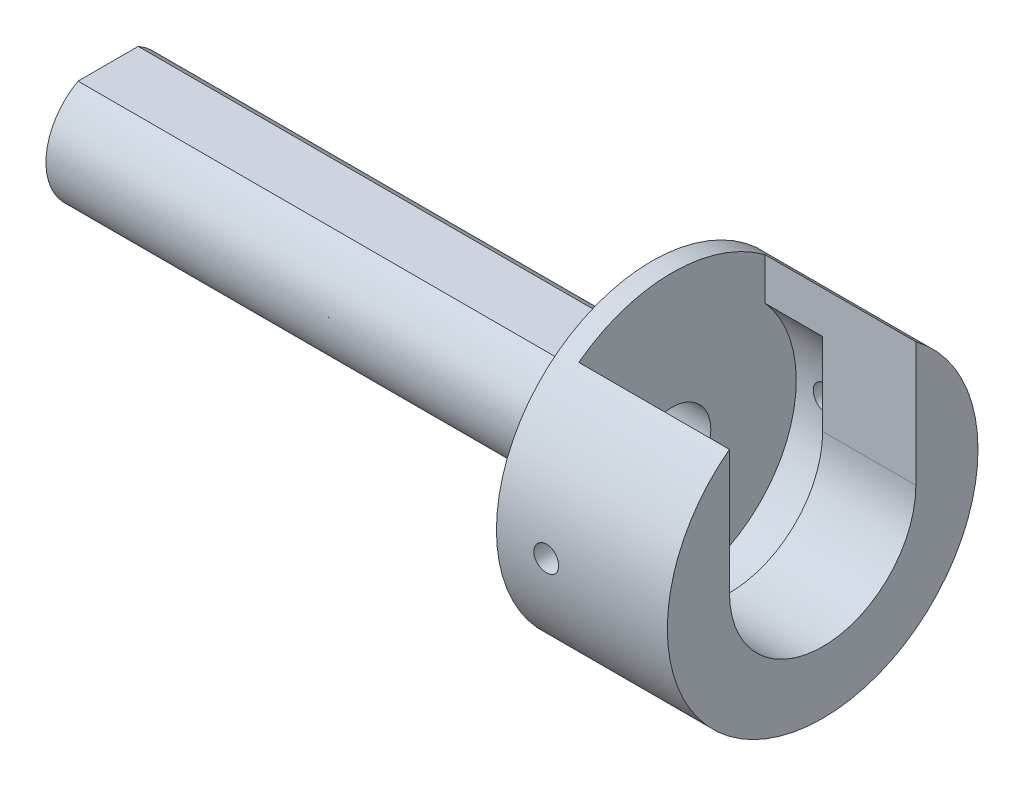
SolidWorks part; units mm, degrees
ref_plane "Front Plane" through (0, 0, 0) normal (0, 0, 1) x (1, 0, 0)
ref_plane "Top Plane" through (0, 0, 0) normal (0, 1, 0) x (1, 0, 0)
ref_plane "Right Plane" through (0, 0, 0) normal (1, 0, 0) x (0, 0, -1)
sketch "Sketch1" plane through (0, 0, 0) normal (1, 0, 0) x (0, 0, -1)
  circle A0 centre (0, 0) radius 10
  dimension "D1" = 20
extrude "Boss-Extrude1" add sketch "Sketch1" along normal blind 11
sketch "Sketch3" plane through (11, 0, 0) normal (1, 0, 0) x (0, 0, -1)
  line L0 (-6, 0) -> (-6, 8)
  line L1 (6, 0) -> (6, 8)
  arc A0 (-6, 0) -> (6, 0) centre (0, 0) ccw
  arc A2 (6, 8) -> (-6, 8) centre (0, 0) ccw
  dimension "D1" = 12
  dimension "D2" = 20
extrude "Cut-Extrude2" cut sketch "Sketch3" against normal blind 9.7
sketch "Sketch4" plane through (1.3, 0, 0) normal (1, 0, 0) x (0, 0, -1)
  circle A0 centre (0, 0) radius 8
  dimension "D1" = 16
extrude "Cut-Extrude3" cut sketch "Sketch4" along normal blind 3.7
sketch "Sketch24" plane through (0, 0, 0) normal (-1, 0, 0) x (0, 0, 1)
  line L0 (-1.9365, 3.5) -> (1.9365, 3.5)
  arc A0 (-1.9365, 3.5) -> (1.9365, 3.5) centre (0, 0) ccw
  dimension "D1" = 8
  dimension "D2" = 3.5
extrude "Boss-Extrude2" add sketch "Sketch24" along normal blind 35
sketch "Sketch2" plane through (0, 0, 0) normal (-1, 0, 0) x (0, 0, 1)
  circle A0 centre (0, 0) radius 2.5
  dimension "D1" = 5
extrude "Cut-Extrude1" cut sketch "Sketch2" against normal through all both and the other way through all
ref_plane "Plane1" through (0, 0, -10) normal (0, 0, 1) x (1, 0, 0)
hole_wizard "M2x0.4 Tapped Hole1" positions "Sketch22" profile "Sketch23" tap size "M2x0.4" standard "ANSI Metric" end condition up to next
sketch "Sketch22" plane through (0, 0, -10) normal (0, 0, 1) x (1, 0, 0)
  line L0 (0, 0) -> (36.8629, 0) construction
  line L2 (11, -10) -> (11, 8) construction
  point P0 (3.2, 0)
  dimension "D1" = 7.8
sketch "Sketch23" plane through (3.2, 0, -10) normal (1, 0, 0) x (0, 1, 0)
  line L0 (0, 0) -> (0, 2)
  line L1 (0, 2) -> (0.8, 2)
  line L2 (0.8, 2) -> (0.8, 0)
  line L5 (0.8, 0) -> (0, 0)
  line L11 (0, -6.35) -> (0, 107.95) construction
  dimension "Thru Tap Drill Dia." = 1.6
  dimension "Thru Tap Drill Depth" = 2
cosmetic thread "Hole Thread10" parameters "D1"=2.0401, "D2"=2
ref_plane "Plane2" through (0, 0, 10) normal (0, 0, 1) x (1, 0, 0)
hole_wizard "M2x0.4 Tapped Hole2" positions "Sketch12" profile "Sketch13" tap size "M2x0.4" standard "ANSI Metric" end condition up to next
sketch "Sketch12" plane through (0, 0, 10) normal (0, 0, 1) x (1, 0, 0)
  line L0 (11, -10) -> (11, 8) construction
  line L2 (0, 0) -> (39.7675, 0) construction
  point P0 (3.2, 0)
  dimension "D1" = 7.8
sketch "Sketch13" plane through (3.2, 0, 10) normal (1, 0, 0) x (0, -1, 0)
  line L0 (0, 0) -> (0, 2)
  line L1 (0, 2) -> (0.8, 2)
  line L2 (0.8, 2) -> (0.8, 0)
  line L5 (0.8, 0) -> (0, 0)
  line L11 (0, -6.35) -> (0, 107.95) construction
  dimension "Thru Tap Drill Dia." = 1.6
  dimension "Thru Tap Drill Depth" = 2
cosmetic thread "Hole Thread11" parameters "D1"=2.0401, "D2"=2
ref_plane "Plane3" through (0, -10, 0) normal (0, 1, 0) x (1, 0, 0)
hole_wizard "M2x0.4 Tapped Hole3" positions "Sketch25" profile "Sketch26" tap size "M2x0.4" standard "ANSI Metric" end condition up to next
sketch "Sketch25" plane through (0, -10, 0) normal (0, 1, 0) x (1, 0, 0)
  line L0 (0, 10) -> (0, -10) construction
  point P0 (3, 0)
  dimension "D1" = 3
sketch "Sketch26" plane through (3, -10, 0) normal (1, 0, 0) x (0, 0, -1)
  line L0 (0, 0) -> (0, 2)
  line L1 (0, 2) -> (0.8, 2)
  line L2 (0.8, 2) -> (0.8, 0)
  line L5 (0.8, 0) -> (0, 0)
  line L11 (0, -6.35) -> (0, 107.95) construction
  dimension "Thru Tap Drill Dia." = 1.6
  dimension "Thru Tap Drill Depth" = 2
cosmetic thread "Hole Thread12" parameters "D1"=2.0401, "D2"=2
